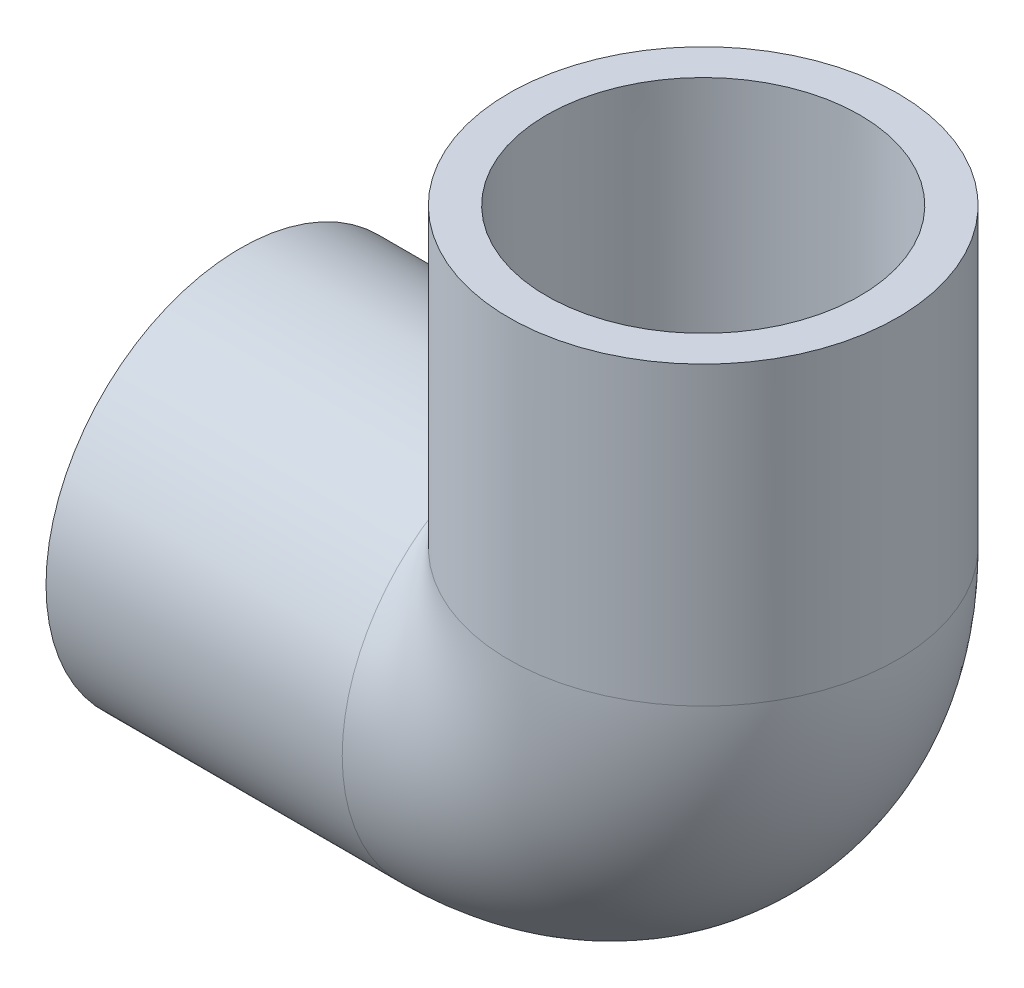
SolidWorks part; units mm, degrees
ref_plane "Front Plane" through (0, 0, 0) normal (0, 0, 1) x (1, 0, 0)
ref_plane "Top Plane" through (0, 0, 0) normal (0, 1, 0) x (1, 0, 0)
ref_plane "Right Plane" through (0, 0, 0) normal (1, 0, 0) x (0, 0, -1)
sketch "Sketch0" plane through (0, 0, 0) normal (0, 0, 1) x (1, 0, 0)
  line L0 (-39.6875, 0) -> (0, 0) construction
  line L1 (0, 0) -> (0, 39.6875) construction
  line L2 (-14.2875, 0) -> (0, 0) construction
  line L3 (0, 0) -> (0, 14.2875) construction
  line L4 (-39.6875, 16.6687) -> (-39.6875, -16.6687) construction
  line L5 (-14.2875, 13.2842) -> (-39.6875, 13.4366) construction
  line L6 (-14.2875, 13.2842) -> (-14.2875, -13.2842) construction
  line L7 (-14.2875, -13.2842) -> (-39.6875, -13.4366) construction
  line L8 (-39.6875, 13.4366) -> (-39.6875, -13.4366) construction
  line L9 (-16.6687, 39.6875) -> (16.6687, 39.6875) construction
  line L10 (-13.4366, 39.6875) -> (13.4366, 39.6875) construction
  line L11 (13.4366, 39.6875) -> (13.2842, 14.2875) construction
  line L12 (13.2842, 14.2875) -> (-13.2842, 14.2875) construction
  line L13 (-13.2842, 14.2875) -> (-13.4366, 39.6875) construction
  line L14 (-14.2875, 10.4648) -> (-14.2875, -10.4648) construction
  line L18 (-10.4648, 14.2875) -> (10.4648, 14.2875) construction
  dimension "H" = 39.6875
  dimension "G" = 14.2875
  dimension "M" = 33.3375
  dimension "OD A" = 26.8732
  dimension "OD B" = 26.5684
  dimension "ID" = 20.9296
sketch "Sketch1" plane through (0, 0, 0) normal (0, 0, 1) x (1, 0, 0)
  line L0 (-39.6875, 0) -> (0, 0) construction
  line L1 (-39.6875, 0) -> (0, 0) construction
  line L3 (-39.6875, -16.6687) -> (-14.2875, -16.6687)
  line L4 (-39.6875, -16.6687) -> (-39.6875, -13.4366)
  line L5 (-39.6875, -13.4366) -> (-14.2875, -13.2842)
  line L6 (-14.2875, -16.6687) -> (-14.2875, -13.2842)
revolve "Revolve1" add sketch "Sketch1" angle 360 about L1
sketch "Sketch2" plane through (0, 0, 0) normal (0, 0, 1) x (1, 0, 0)
  line L0 (13.4366, 39.6875) -> (13.2842, 14.2875)
  line L1 (13.2842, 14.2875) -> (16.6687, 14.2875)
  line L2 (16.6687, 14.2875) -> (16.6687, 39.6875)
  line L3 (16.6687, 39.6875) -> (13.4366, 39.6875)
  line L4 (0, 0) -> (0, 39.6875) construction
  line L5 (0, 0) -> (0, 39.6875) construction
revolve "Revolve2" add sketch "Sketch2" angle 360 about L5
sketch "Sketch3" plane through (-14.2875, 0, 0) normal (1, 0, 0) x (0, 0, -1)
  circle A0 centre (0, 0) radius 10.4648
  circle A1 centre (0, 0) radius 16.6687
sketch "Sketch4" plane through (0, 0, 0) normal (0, 0, 1) x (1, 0, 0)
  line L0 (-39.6875, 0) -> (0, 0) construction
  line L1 (0, 0) -> (0, 39.6875) construction
  line L2 (-39.6875, 0) -> (-14.2875, 0) construction
  line L3 (0, 14.2875) -> (0, 39.6875) construction
  arc A0 (-14.2875, 0) -> (0, 14.2875) centre (-14.2875, 14.2875) ccw
sweep "Sweep1" add profiles "Sketch3" path "Sketch4"
